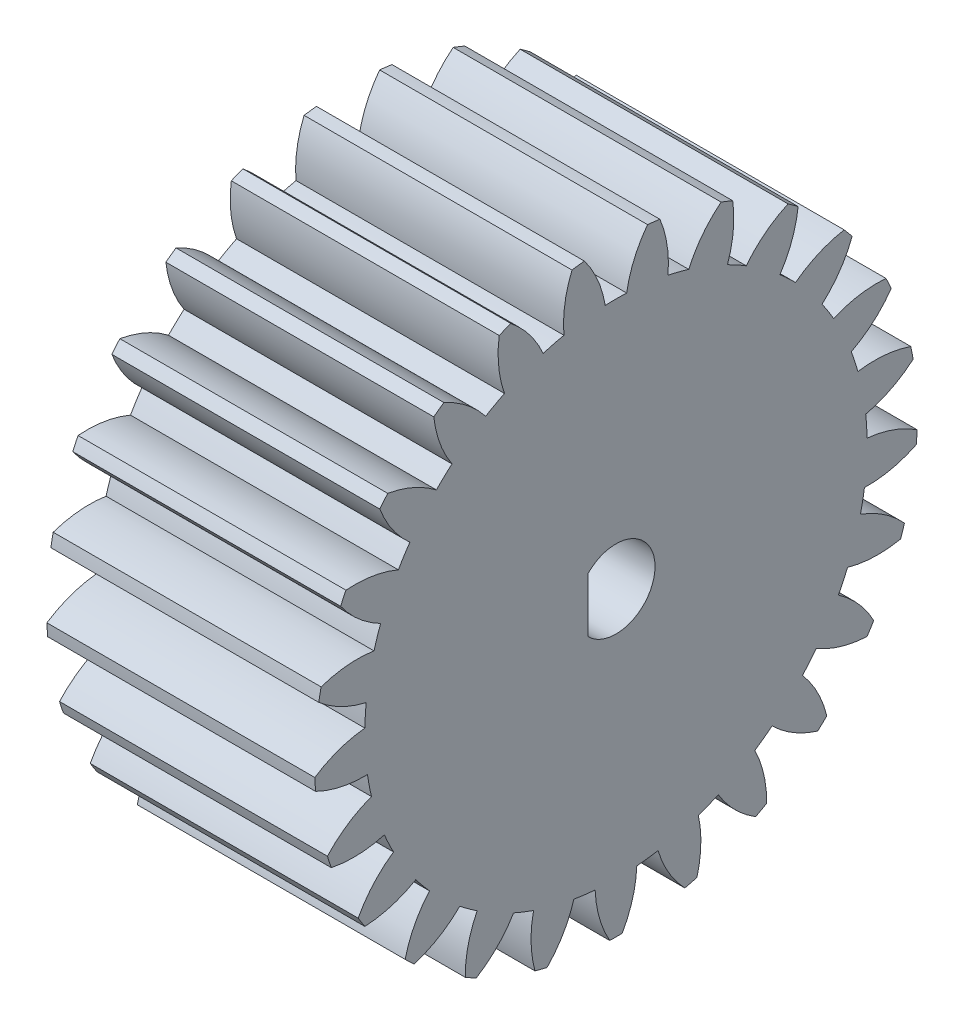
SolidWorks part; units mm, degrees
ref_plane "Plane1" through (0, 0, 0) normal (0, 0, 1) x (1, 0, 0)
ref_plane "Plane2" through (0, 0, 0) normal (0, 1, 0) x (1, 0, 0)
ref_plane "Plane3" through (0, 0, 0) normal (1, 0, 0) x (0, 0, -1)
sketch "HoldingSke" plane through (0, 0, 0) normal (0, 1, 0) x (1, 0, 0)
  line L0 (0, 0) -> (0.9063, -0.4226)
  line L1 (-15, 0) -> (100, 0) construction
  line L2 (0, 0) -> (-2.1039, 2.3779)
  line L3 (0, 0) -> (-11.863, 4.5341)
  line L4 (0, 0) -> (7.8269, 3.6497)
  line L5 (0, 0) -> (-46.8476, -17.4728)
  line L6 (0, 0) -> (-9.9476, -6.7116)
  line L7 (-2.1039, 2.3779) -> (8.6586, 51.2059)
  line L8 (-76.2, 54.61) -> (-75.7, 54.61)
  line L9 (-71.009, 38.7566) -> (-53.1078, 45.2721)
  line L10 (-76.2, 71.12) -> (104.1128, 71.12)
  line L11 (0, 0) -> (-12, 0)
  line L12 (-76.2, 101.6) -> (-76.162, 101.6)
  line L13 (24.9733, 27.94) -> (52.9518, 28.4284)
  line L14 (24.9733, 27.94) -> (24.9743, 27.94)
  line L15 (24.9733, 27.94) -> (100.4006, 29.5858)
  line L16 (-63.627, -1) -> (-12.827, -1)
  circle A0 centre (0, 0) radius 1.5
  circle A1 centre (0, 0) radius 11.249
  circle A2 centre (0, 0) radius 37.5
  circle A3 centre (0, 0) radius 1.5
  dimension "Num_teeth" = 25
  dimension "Pitch_radius" = 180.3128
  dimension "Width" = 12
  dimension "Thickness" = 12
sketch "BasProSke" plane through (0, 0, 0) normal (0, 1, 0) x (1, 0, 0)
  line L0 (-10, 0) -> (60, 0) construction
  line L1 (0, 0) -> (0, 13.5)
  line L2 (0, 0) -> (12, 0)
  line L3 (12, 0) -> (12, 13.5)
  line L4 (12, 13.5) -> (0, 13.5)
  dimension "Thickness" = 12
  dimension "Diameter" = 27
revolve "Base-Revolve" add sketch "BasProSke" angle 360 about L0
sketch "TooCutSke" plane through (0, 0, 0) normal (1, 0, 0) x (0, 0, -1)
  line L1 (0, 0) -> (0, 107) construction
  line L2 (0, 0) -> (-0.8514, 12.471) construction
  line L3 (0, 0) -> (-3.1282, 24.7619) construction
  line L4 (-0.8514, 12.471) -> (-1.5641, 12.3809) construction
  arc A0 (0.4801, 11.2388) -> (-0.4801, 11.2388) centre (0, 0) ccw
  arc A1 (1.4322, 13.4494) -> (-1.4322, 13.4494) centre (0, 0) ccw
  circle A2 centre (0, 0) radius 12.5 construction
  circle A3 centre (0, 0) radius 11.7462 construction
  arc A4 (-0.4801, 11.2388) -> (-1.4322, 13.4494) centre (-5.4133, 10.4244) ccw
  arc A5 (1.4322, 13.4494) -> (0.4801, 11.2388) centre (5.4133, 10.4244) ccw
extrude "ToothCut" cut sketch "TooCutSke" along normal through all
fillet "Breaks" [suppressed] radius 0.02 tangent propagation no
fillet "RootFillets" [suppressed] radius 0.251
pattern_circular "TeethCuts" count 25 every 14.4 about axis through (-10, 0, 0) along (1, 0, 0) of "ToothCut", "RootFillets", "Breaks"
sketch "HubNeaOneSke" plane through (0, 0, 0) normal (-1, 0, 0) x (0, 0, 1)
  circle A0 centre (0, 0) radius 11.249
  dimension "Diameter" = 22.498
extrude "HubNearOne" [suppressed] add sketch "HubNeaOneSke" along normal blind 38.0001
sketch "HubNeaBotSke" plane through (0, 0, 0) normal (-1, 0, 0) x (0, 0, 1)
  circle A0 centre (0, 0) radius 11.249
  dimension "Diameter" = 22.498
extrude "HubNearBoth" [suppressed] add sketch "HubNeaBotSke" along normal blind 19
ref_plane "FarPln" through (12, 0, 0) normal (1, 0, 0) x (0, 0, -1)
sketch "HubFarSke" plane through (12, 0, 0) normal (1, 0, 0) x (0, 0, -1)
  circle A0 centre (0, 0) radius 11.249
  dimension "Diameter" = 22.498
extrude "HubFar" [suppressed] add sketch "HubFarSke" along normal blind 19
sketch "BorSke" plane through (0, 0, 0) normal (1, 0, 0) x (0, 0, -1)
  circle A0 centre (0, 0) radius 1.5
  dimension "Diameter" = 3
extrude "Bore" cut sketch "BorSke" along normal mid plane 100.0001
sketch "KeySke" plane through (0, 0, 0) normal (1, 0, 0) x (0, 0, -1)
  line L0 (-0.6, 0) -> (-0.6, 2)
  line L1 (-0.6, 2) -> (0.6, 2)
  line L2 (0.6, 2) -> (0.6, 0)
  line L3 (0, 0) -> (0, 34) construction
  line L4 (-0.6, 0) -> (0.6, 0)
extrude "Keyway" [suppressed] cut sketch "KeySke" along normal mid plane 100.0001
pattern_circular "Keyway2" [suppressed] count 2 every 90 about axis through (-10, 0, 0) along (1, 0, 0) reverse direction yes
sketch "Sketch1" plane through (12, 0, 0) normal (1, 0, 0) x (0, 0, -1)
  line L0 (-1, 1.118) -> (-1, -1.118)
  line L1 (-1.25, 1.2247) -> (-1.25, -1.2247)
  circle A0 centre (0, 0) radius 1.5 construction
  arc A1 (-1, -1.118) -> (-1, 1.118) centre (0, 0) ccw
  arc A2 (-1.25, -1.2247) -> (-1.25, 1.2247) centre (0, 0) ccw
  circle A3 centre (0, 0) radius 1.5
  dimension "D1" = 1
  dimension "D2" = 0.25
extrude "Cut-Extrude1" cut sketch "Sketch1" against normal through all contours A3 A1 L1 A2 region at (12, 1.0118, 1.1691)
extrude "Boss-Extrude2" add sketch "Sketch1<4>" against normal through all contours L1 A3 region at (12, 0, 1.3508)
sketch "Sketch1<4>" plane through (12, 0, 0) normal (1, 0, 0) x (0, 0, -1) same geometry as "Sketch1"
equation "' \"Module@HoldingSke\" = 6.35"
equation "' \"Num_teeth@HoldingSke\" = 12"
equation "' \"Ap@HoldingSke\" =  20"
equation "' \"Ap@HoldingSke\" = 20"
equation "' \"Width@HoldingSke\" = 0.5 * 25.4"
equation "' \"Hub_dia@HoldingSke\"= 1 * 25.4"
equation "' \"Hub_dia@HoldingSke\" = 1 * 25.4"
equation "' \"Overall_len@HoldingSke\" = 1.0 * 25.4"
equation "' \"Bore@HoldingSke\" = 0.75 * 25.4"
equation "' \"T_dim@HoldingSke\" = 0.1 * 25.4"
equation "' \"Width@KeySke\" = 0.25 * 25.4"
equation "' \"Show_teeth@HoldingSke\" = 13"
equation "' \"Backlash@HoldingSke\" = 0.009 * 25.4"
equation "' \"Addendum_fac@HoldingSke\" = 1.0"
equation "' \"Dedendum_fac@HoldingSke\" = 1.25"
equation "' \"Dedendum_add@HoldingSke\" = 0.00005 * 25.4"
equation "' \"Clearance_fac@HoldingSke\" = 0.25"
equation "\"Pitch@HoldingSke\" = 1 / \"Module@HoldingSke\""
equation "\"Overcut_dia@TooCutSke\" = (\"Num_teeth@HoldingSke\" + 2 * \"Addendum_fac@HoldingSke\") / \"Pitch@HoldingSke\" + 0.002 * 25.4"
equation "\"Pitch_dia@TooCutSke\" = \"Num_teeth@HoldingSke\" / \"Pitch@HoldingSke\""
equation "\"Base_dia@TooCutSke\" = \"Num_teeth@HoldingSke\" / \"Pitch@HoldingSke\" * cos((\"Ap@HoldingSke\"  * 3.14159265 / 180))"
equation "\"Root_dia@TooCutSke\" = (\"Num_teeth@HoldingSke\" + 2) / \"Pitch@HoldingSke\" - 2 * (\"Addendum_fac@HoldingSke\" + \"Dedendum_fac@HoldingSke\") / \"Pitch@HoldingSke\" - \"Dedendum_add@HoldingSke\" * 2"
equation "\"Half_ang@TooCutSke\" = 180 / \"Num_teeth@HoldingSke\""
equation "\"Half_CT@TooCutSke\" = \"Num_teeth@HoldingSke\" / \"Pitch@HoldingSke\" * sin((3.14159265 / 2 / \"Num_teeth@HoldingSke\")) / 2 - 7 * \"Backlash@HoldingSke\" / 4"
equation "\"Flank_rad@TooCutSke\" = \"Num_teeth@HoldingSke\" / \"Pitch@HoldingSke\" / 5"
equation "\"Radius@RootFillets\" = \"Clearance_fac@HoldingSke\" / \"Pitch@HoldingSke\" + \"Dedendum_add@HoldingSke\""
equation "\"Break_rad@Breaks\" = 0.02 / \"Pitch@HoldingSke\""
equation "\"Thickness@HoldingSke\" = \"Width@HoldingSke\""
equation "\"OAL@HoldingSke\" = \"Thickness@HoldingSke\""
equation "\"MHD@HoldingSke\" = (\"Num_teeth@HoldingSke\" + 2) / \"Pitch@HoldingSke\" - 2 * (\"Addendum_fac@HoldingSke\" + \"Dedendum_fac@HoldingSke\")  / \"Pitch@HoldingSke\" - \"Dedendum_add@HoldingSke\" * 2"
equation "\"MBD@HoldingSke\" = (\"Num_teeth@HoldingSke\" + 2) / \"Pitch@HoldingSke\" - 2 * (\"Addendum_fac@HoldingSke\" + \"Dedendum_fac@HoldingSke\")  / \"Pitch@HoldingSke\" - \"Dedendum_add@HoldingSke\" * 2 - 0.002 * 25.4"
equation "\"MHD@HoldingSke\" = ((sgn( \"MHD@HoldingSke\" - \"Hub_dia@HoldingSke\" )-1)*( \"MHD@HoldingSke\" - \"Hub_dia@HoldingSke\" ))/-2+ \"Hub_dia@HoldingSke\""
equation "\"MBD@HoldingSke\" = ((sgn( \"MBD@HoldingSke\" - \"Bore@HoldingSke\" )-1)*( \"MBD@HoldingSke\" - \"Bore@HoldingSke\" ))/-2+ \"Bore@HoldingSke\""
equation "\"OAL@HoldingSke\" = ((sgn( \"OAL@HoldingSke\" - \"Overall_len@HoldingSke\" )+1)*( \"OAL@HoldingSke\" - \"Overall_len@HoldingSke\" ))/2 + \"Overall_len@HoldingSke\" + 0.000002 * 25.4"
equation "\"Num_teeth@TeethCuts\" = int( \"Show_teeth@HoldingSke\" ) + 1"
equation "\"Num_teeth@TeethCuts\" = ((sgn( \"Num_teeth@TeethCuts\" - \"Num_teeth@HoldingSke\" )-1)*( \"Num_teeth@TeethCuts\" - \"Num_teeth@HoldingSke\" ))/-2+ \"Num_teeth@HoldingSke\""
equation "\"Num_teeth@TeethCuts\" = ((sgn( \"Num_teeth@TeethCuts\" - 2.0)+1)*( \"Num_teeth@TeethCuts\" - 2.0))/2 +2.0"
equation "\"Angle@TeethCuts\" = 360.0 / \"Num_teeth@HoldingSke\""
equation "\"Diameter@BasProSke\" = (\"Num_teeth@HoldingSke\" + 2 * \"Addendum_fac@HoldingSke\") / \"Pitch@HoldingSke\""
equation "\"Thickness@BasProSke\"  = \"Thickness@HoldingSke\""
equation "' \"Fillet_rad@BasProSke\" =  \"Thickness@HoldingSke\" * 0.05"
equation "' \"Fillet_rad@BasProSke\" = \"Thickness@HoldingSke\" * 0.05"
equation "\"MHD@HoldingSke\" = ((sgn( \"MHD@HoldingSke\" - \"Root_dia@TooCutSke\" )-1)*( \"MHD@HoldingSke\" - \"Root_dia@TooCutSke\" ))/-2+ \"Root_dia@TooCutSke\""
equation "\"Diameter@HubNeaOneSke\" = \"MHD@HoldingSke\""
equation "\"Length@HubNearOne\" = \"OAL@HoldingSke\" - \"Thickness@BasProSke\""
equation "\"Diameter@HubNeaBotSke\" = \"MHD@HoldingSke\""
equation "\"Length@HubNearBoth\" = ( \"OAL@HoldingSke\" - \"Thickness@BasProSke\" ) / 2.0"
equation "\"Thickness@FarPln\" = \"Thickness@BasProSke\""
equation "\"Diameter@HubFarSke\" = \"MHD@HoldingSke\""
equation "\"Length@HubFar\" = ( \"OAL@HoldingSke\" - \"Thickness@BasProSke\" ) / 2.0"
equation "\"Diameter@BorSke\" = \"MBD@HoldingSke\""
equation "\"D1@Bore\" = \"OAL@HoldingSke\" * 2.0"
equation "\"D1@Keyway\" = \"OAL@HoldingSke\" * 2.0"
equation "\"Offset@KeySke\" = \"T_dim@HoldingSke\" + \"MBD@HoldingSke\" / 2.0"
